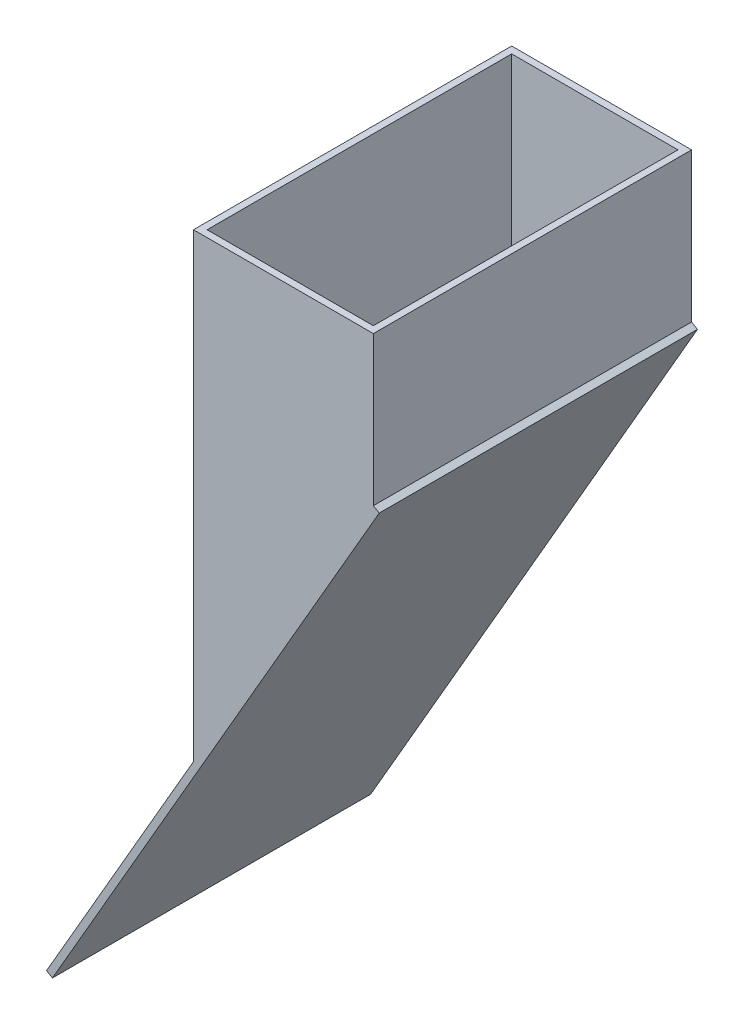
SolidWorks part; units mm, degrees
ref_plane "Front Plane" through (0, 0, 0) normal (0, 0, 1) x (1, 0, 0)
ref_plane "Top Plane" through (0, 0, 0) normal (0, 1, 0) x (1, 0, 0)
ref_plane "Right Plane" through (0, 0, 0) normal (1, 0, 0) x (0, 0, -1)
sketch "Sketch1" plane through (0, 0, 0) normal (0, 1, 0) x (1, 0, 0)
  line L1 (-77.5, 142) -> (77.5, 142)
  line L2 (-77.5, 142) -> (-77.5, -142)
  line L3 (-77.5, -142) -> (77.5, -142)
  line L4 (77.5, 142) -> (77.5, -142)
  line L5 (-77.5, 142) -> (77.5, -142) construction
  line L6 (-77.5, -142) -> (77.5, 142) construction
  line L7 (-83.85, 148.35) -> (83.85, 148.35)
  line L8 (-83.85, 148.35) -> (-83.85, -148.35)
  line L9 (-83.85, -148.35) -> (83.85, -148.35)
  line L10 (83.85, 148.35) -> (83.85, -148.35)
  line L11 (-83.85, 148.35) -> (83.85, -148.35) construction
  line L12 (-83.85, -148.35) -> (83.85, 148.35) construction
  point P0 (0, 0)
  point P5 (0, 0)
  dimension "D1" = 284
  dimension "D2" = 155
  dimension "D3" = 6.35
  dimension "D4" = 6.35
sketch3d "3DSketch1"
  line L0 (77.5, 0, 0) -> (77.5, -150, 0) construction
  line L1 (77.5, 0, -142) -> (77.5, 0, 142) construction
  line L2 (77.5, -150, 102.7398) -> (77.5, -150, -102.7398) construction
  dimension "D1" = 150
ref_plane "Base Plane" through (123.0769, -71.0585, 0) normal (-0.866, 0.5, 0) x (0, 0, -1)
extrude "Boss-Extrude1" add sketch "Sketch1" against normal up to surface (150 mm away) up to plane "Base Plane"
sketch "Sketch3" plane through (123.0769, -71.0585, 0) normal (-0.866, 0.5, 0) x (0, 0, -1)
  line L0 (-148.35, 413.8538) -> (148.35, 413.8538) construction
  line L1 (148.35, 687.8538) -> (-148.35, 687.8538)
  line L2 (148.35, 687.8538) -> (148.35, 78.4538)
  line L3 (148.35, 78.4538) -> (-148.35, 78.4538)
  line L4 (-148.35, 687.8538) -> (-148.35, 78.4538)
  dimension "D1" = 274
extrude "Boss-Extrude2" add sketch "Sketch3" against normal blind 6.35
sketch "Sketch4" plane through (0, 0, 0) normal (0, 0, 1) x (1, 0, 0)
  line L0 (-83.85, -429.4664) -> (-77.5, -418.4679)
  line L1 (-83.85, -333.4679) -> (-77.5, -333.4679)
  line L2 (-77.5, -418.4679) -> (-77.5, 0) construction
  line L3 (-83.85, -429.4664) -> (-83.85, -333.4679)
  line L4 (-83.85, -429.4664) -> (-83.85, 0) construction
  line L5 (-77.5, -333.4679) -> (-77.5, -418.4679)
  line L6 (179.5838, 26.8143) -> (66.57, -168.9313) construction
  dimension "D2" = 85
extrude "Cut-Extrude1" cut sketch "Sketch4" against normal up to surface and the other way up to surface up to face at (0, -142.117, -142) other way up to face at (0, -142.117, 142)
equation "\"Frisbee Width\"=274"
equation "\"D1@Sketch1\"=\"Frisbee Width\"+10"
equation "\"Wall Thickness\"= 6.35"
equation "\"D3@Sketch1\"=\"Wall Thickness\""
equation "\"D4@Sketch1\"=\"Wall Thickness\""
equation "\"D1@Boss-Extrude2\"=\"Wall Thickness\""
equation "\"D1@Sketch3\"=\"Frisbee Width\""
